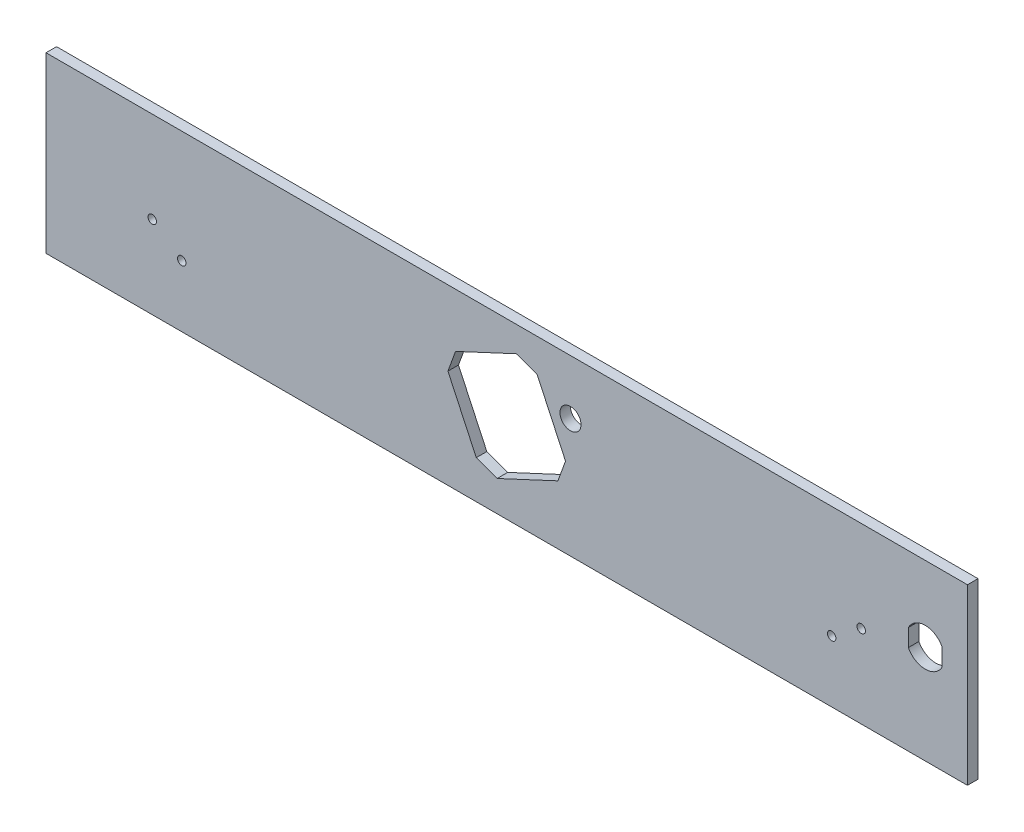
SolidWorks part; units mm, degrees
ref_plane "Front (1)" through (0, 0, 0) normal (0, 0, 1) x (1, 0, 0)
ref_plane "Top (2)" through (0, 0, 0) normal (0, 1, 0) x (1, 0, 0)
ref_plane "Right (3)" through (0, 0, 0) normal (1, 0, 0) x (0, 0, -1)
ref_axis "X-Axis" through (-80.9, 0, 0) along (1, 0, 0)
ref_axis "Y-Axis" through (0, -50, 0) along (0, 1, 0)
ref_axis "Z-Axis" through (0, 0, 50) along (0, 0, -1)
sketch "Sketch1" plane through (0, 0, 0) normal (0, 0, 1) x (1, 0, 0)
  line L1 (0, 0) -> (415.925, 0)
  line L2 (0, 0) -> (0, 78.4225)
  line L3 (0, 78.4225) -> (415.925, 78.4225)
  line L4 (415.925, 0) -> (415.925, 78.4225)
  dimension "D1" = 415.925
  dimension "D2" = 78.4225
extrude "Boss-Extrude1" add sketch "Sketch1" along normal blind 4.7625
sketch "Sketch2" plane through (0, 0, 0) normal (0, 0, -1) x (-1, 0, 0)
  line L0 (-367.9825, 37.3063) -> (-207.9625, 0) construction
  line L1 (0, 0) -> (-415.925, 0) construction
  line L2 (-207.9625, 0) -> (-47.9425, 37.3063) construction
  line L3 (-354.6475, 27.7813) -> (-207.9625, 78.4225) construction
  line L4 (-415.925, 78.4225) -> (0, 78.4225) construction
  line L5 (-207.9625, 78.4225) -> (-61.2775, 27.7813) construction
  line L6 (0, 0) -> (-415.925, 0) construction
  circle A0 centre (-367.9825, 37.3063) radius 1.905
  circle A1 centre (-354.6475, 27.7813) radius 1.905
  circle A2 centre (-47.9425, 37.3063) radius 1.905
  circle A3 centre (-61.2775, 27.7813) radius 1.905
  dimension "D9" = 3.81
  dimension "D1" = 13.335
  dimension "D2" = 37.3062
  dimension "D3" = 320.04
  dimension "D4" = 9.525
  dimension "D8" = 9.525
extrude "Cut-Extrude1" cut sketch "Sketch2" against normal through all
sketch "Sketch3" plane through (0, 0, 4.7625) normal (0, 0, 1) x (1, 0, 0)
  line L0 (389.255, 48.3773) -> (389.255, 40.5227)
  line L1 (415.925, 0) -> (415.925, 78.4225) construction
  line L2 (404.495, 40.5227) -> (404.495, 48.3773)
  line L3 (0, 0) -> (415.925, 0) construction
  circle A0 centre (396.875, 44.45) radius 8.5725
  dimension "D1" = 17.145
  dimension "D2" = 15.24
  dimension "D3" = 19.05
  dimension "D4" = 44.45
extrude "Cut-Extrude2" cut sketch "Sketch3" against normal through all contours L2 A0 L0 region at (396.875, 44.45, 4.7625)
sketch "Sketch4" plane through (0, 0, 0) normal (0, 0, 1) x (1, 0, 0)
  line L0 (63.5, 6.35) -> (0, 6.35) construction
  line L2 (0, 0) -> (415.925, 0) construction
  line L3 (0, 78.4225) -> (0, 0) construction
  text T0 "<b>LCSAP-602</b>"
  dimension "D1" = 63.5
  dimension "D2" = 6.35
extrude "Cut-Extrude3" cut sketch "Sketch4" along normal blind 1.016
sketch "Sketch5" plane through (0, 0, 4.7625) normal (0, 0, 1) x (1, 0, 0)
  line L0 (184.8548, 54.1015) -> (212.2848, 66.8924)
  line L1 (212.2848, 66.8924) -> (221.7098, 63.462)
  line L2 (221.7098, 63.462) -> (234.5006, 36.0319)
  line L3 (234.5006, 36.0319) -> (231.0702, 26.607)
  line L4 (231.0702, 26.607) -> (203.6402, 13.8161)
  line L5 (203.6402, 13.8161) -> (194.2152, 17.2465)
  line L6 (194.2152, 17.2465) -> (181.4244, 44.6766)
  line L7 (181.4244, 44.6766) -> (184.8548, 54.1015)
  line L8 (198.5698, 60.4969) -> (207.9625, 40.3543) construction
  line L9 (207.9625, 40.3543) -> (228.1052, 49.7469) construction
  line L10 (415.925, 0) -> (0, 0) construction
  line L14 (415.925, 0) -> (415.925, 78.4225) construction
  line L15 (0, 0) -> (415.925, 0) construction
  line L16 (228.1052, 49.7469) -> (236.7378, 53.7724) construction
  circle A0 centre (236.7378, 53.7724) radius 4.7625
  dimension "D7" = 9.525
  dimension "D1" = 44.45
  dimension "D2" = 52.832
  dimension "D3" = 135
  dimension "D4" = 25
  dimension "D5" = 207.9625
  dimension "D6" = 40.3543
  dimension "D8" = 9.525
extrude "Cut-Extrude4" cut sketch "Sketch5" against normal through all
